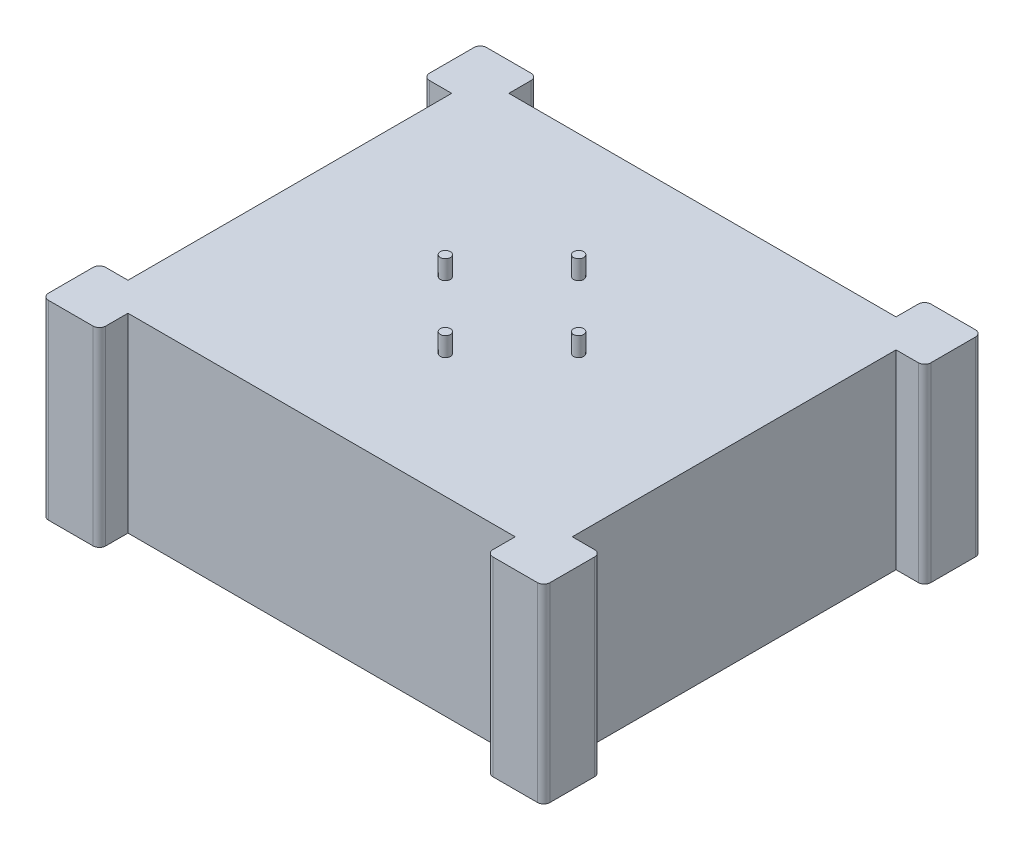
SolidWorks part; units mm, degrees
material "1060 Alloy"
ref_plane "Front Plane" through (0, 0, 0) normal (0, 0, 1) x (1, 0, 0)
ref_plane "Top Plane" through (0, 0, 0) normal (0, 1, 0) x (1, 0, 0)
ref_plane "Right Plane" through (0, 0, 0) normal (1, 0, 0) x (0, 0, -1)
sketch "Sketch1" plane through (0, 0, 0) normal (0, 1, 0) x (1, 0, 0)
  line L0 (-175, 0) -> (175, 0) construction
  line L1 (-175, 150) -> (175, 150)
  line L2 (-175, 150) -> (-175, -150)
  line L3 (-175, -150) -> (175, -150)
  line L4 (175, 150) -> (175, -150)
  line L5 (-175, 172.5) -> (-175, 127.5) construction
  line L6 (-192.5, 172.5) -> (-157.5, 172.5)
  line L7 (-197.5, 167.5) -> (-197.5, 132.5)
  line L8 (-192.5, 127.5) -> (-157.5, 127.5)
  line L9 (-152.5, 167.5) -> (-152.5, 132.5)
  line L10 (157.5, 172.5) -> (192.5, 172.5)
  line L11 (152.5, 167.5) -> (152.5, 132.5)
  line L12 (157.5, 127.5) -> (192.5, 127.5)
  line L13 (197.5, 167.5) -> (197.5, 132.5)
  line L14 (175, 172.5) -> (175, 127.5) construction
  line L15 (157.5, -127.5) -> (192.5, -127.5)
  line L16 (152.5, -132.5) -> (152.5, -167.5)
  line L17 (157.5, -172.5) -> (192.5, -172.5)
  line L18 (197.5, -132.5) -> (197.5, -167.5)
  line L19 (175, -127.5) -> (175, -172.5) construction
  line L20 (-192.5, -127.5) -> (-157.5, -127.5)
  line L21 (-197.5, -132.5) -> (-197.5, -167.5)
  line L22 (-192.5, -172.5) -> (-157.5, -172.5)
  line L23 (-152.5, -132.5) -> (-152.5, -167.5)
  line L24 (-175, -127.5) -> (-175, -172.5) construction
  line L26 (-170, 145) -> (170, 145)
  line L27 (-170, 145) -> (-170, -145)
  line L28 (-170, -145) -> (170, -145)
  line L29 (170, 145) -> (170, -145)
  circle A0 centre (0, 0) radius 52.5 construction
  circle A1 centre (0, 52.5) radius 4
  circle A2 centre (0, -52.5) radius 4
  circle A3 centre (52.5, 0) radius 4
  circle A4 centre (-52.5, 0) radius 4
  arc A5 (-157.5, 172.5) -> (-152.5, 167.5) centre (-157.5, 167.5) cw
  arc A6 (-157.5, 127.5) -> (-152.5, 132.5) centre (-157.5, 132.5) ccw
  arc A7 (-197.5, 132.5) -> (-192.5, 127.5) centre (-192.5, 132.5) ccw
  arc A8 (-192.5, 172.5) -> (-197.5, 167.5) centre (-192.5, 167.5) ccw
  arc A9 (192.5, 172.5) -> (197.5, 167.5) centre (192.5, 167.5) cw
  arc A10 (192.5, 127.5) -> (197.5, 132.5) centre (192.5, 132.5) ccw
  arc A11 (152.5, 132.5) -> (157.5, 127.5) centre (157.5, 132.5) ccw
  arc A12 (157.5, 172.5) -> (152.5, 167.5) centre (157.5, 167.5) ccw
  arc A13 (192.5, -127.5) -> (197.5, -132.5) centre (192.5, -132.5) cw
  arc A14 (192.5, -172.5) -> (197.5, -167.5) centre (192.5, -167.5) ccw
  arc A15 (152.5, -167.5) -> (157.5, -172.5) centre (157.5, -167.5) ccw
  arc A16 (157.5, -127.5) -> (152.5, -132.5) centre (157.5, -132.5) ccw
  arc A17 (-157.5, -127.5) -> (-152.5, -132.5) centre (-157.5, -132.5) cw
  arc A18 (-157.5, -172.5) -> (-152.5, -167.5) centre (-157.5, -167.5) ccw
  arc A19 (-197.5, -167.5) -> (-192.5, -172.5) centre (-192.5, -167.5) ccw
  arc A20 (-192.5, -127.5) -> (-197.5, -132.5) centre (-192.5, -132.5) ccw
  point P31 (-175, 150)
  point P34 (175, -150)
  point P76 (-175, -150)
  dimension "D1" = 105
  dimension "D2" = 8
  dimension "D3" = 8
  dimension "D4" = 8
  dimension "D5" = 8
  dimension "D10" = 5
  dimension "D6" = 350
  dimension "D7" = 300
  dimension "D8" = 45
  dimension "D9" = 45
  dimension "D13" = 5
  dimension "D14" = 5
  dimension "D15" = 5
  dimension "D16" = 5
  dimension "D11" = 2
  dimension "D12" = 2
extrude "Boss-Extrude1" add sketch "Sketch1" against normal blind 3 contours L1 L4 L3 L2
extrude "Boss-Extrude2" add sketch "Sketch1<3>" along normal blind 15 contours A1 | A3 | A2 | A4 region at (0, 0, -52.5) region at (0, 0, 52.5) region at (52.5, 0, 0) region at (-52.5, 0, 0)
sketch "Sketch1<3>" plane through (0, 0, 0) normal (0, 1, 0) x (1, 0, 0) same geometry as "Sketch1"
extrude "Boss-Extrude3" add sketch "Sketch1<4>" against normal blind 150 contours L6 A8 L7 A7 L8 L2 L1 L9 A5 | L12 L29 L15 L4 | L9 L26 L11 L1 | L27 L8 L2 L20 | L20 A20 L21 A19 L22 A18 L23 L3 L2 | L28 L23 L3 L16 | L16 A15 L17 A14 L18 A13 L15 L4 L3 | L13 A10 L12 A11 L11 A12 L10 A9 | L23 A18 L22 A19 L21 A20 L20 A17 | A16 L16 A15 L17 A14 L18 A13 L15 | L8 A6 L9 A5 L6 A8 L7 A7 region at (-178.7138, 0, -153.7138) region at (0, 0, -147.5) region at (-172.5, 0, 0) region at (-178.7138, 0, 153.7138) region at (172.5, 0, 0) region at (0, 0, 147.5) region at (178.7138, 0, 153.7138)
sketch "Sketch1<4>" plane through (0, 0, 0) normal (0, 1, 0) x (1, 0, 0) same geometry as "Sketch1"
sketch "Sketch3" plane through (-175, 0, 0) normal (-1, 0, 0) x (0, 0, 1)
  line L2 (-58.1733, -77.2109) -> (-86.3191, -60.9609) construction
  line L3 (-86.3191, -60.9609) -> (-58.1733, -77.2109) construction
  line L4 (-58.1733, -77.2109) -> (-58.1733, -44.7109) construction
  line L5 (-85.2663, -59.2605) -> (-61.1427, -73.1882)
  line L6 (-60.1723, -44.7725) -> (-60.1723, -72.628)
  line L7 (-31.0803, -59.2605) -> (-55.2038, -73.1882)
  line L8 (-56.1742, -44.7725) -> (-56.1742, -72.628)
  line L9 (-29.0812, -91.6989) -> (-53.2048, -77.7712)
  line L10 (-29.0812, -62.7229) -> (-53.2048, -76.6507)
  line L11 (-56.1742, -109.6494) -> (-56.1742, -81.7939)
  line L12 (-31.0803, -95.1614) -> (-55.2038, -81.2337)
  line L13 (-85.2663, -95.1614) -> (-61.1427, -81.2337)
  line L14 (-60.1723, -109.6494) -> (-60.1723, -81.7939)
  line L15 (-87.2653, -62.7229) -> (-63.1418, -76.6507)
  line L16 (-87.2653, -91.6989) -> (-63.1418, -77.7712)
  circle A0 centre (-58.1733, -77.2109) radius 32.5
  arc A3 (-81.3606, -61.5154) -> (-60.1723, -49.2824) centre (-58.1733, -77.2109) cw
  arc A4 (-78.755, -63.0197) -> (-60.1723, -52.291) centre (-58.1733, -77.2109) cw
  arc A5 (-70.0482, -68.0466) -> (-60.1723, -62.3447) centre (-58.1733, -77.2109) cw
  circle A6 centre (-58.1733, -77.2109) radius 5
  arc A7 (-67.4208, -69.5636) -> (-60.1723, -65.3786) centre (-58.1733, -77.2109) cw
  arc A8 (-56.1742, -49.2824) -> (-34.986, -61.5154) centre (-58.1733, -77.2109) cw
  arc A9 (-56.1742, -52.291) -> (-37.5915, -63.0197) centre (-58.1733, -77.2109) cw
  arc A10 (-56.1742, -62.3447) -> (-46.2983, -68.0466) centre (-58.1733, -77.2109) cw
  arc A11 (-56.1742, -65.3786) -> (-48.9257, -69.5636) centre (-58.1733, -77.2109) cw
  arc A12 (-32.9869, -64.9779) -> (-32.9869, -89.444) centre (-58.1733, -77.2109) cw
  arc A13 (-35.5924, -66.4822) -> (-35.5924, -87.9397) centre (-58.1733, -77.2109) cw
  arc A14 (-44.2992, -71.5091) -> (-44.2992, -82.9128) centre (-58.1733, -77.2109) cw
  arc A15 (-46.9266, -73.026) -> (-46.9266, -81.3959) centre (-58.1733, -77.2109) cw
  arc A16 (-34.986, -92.9064) -> (-56.1742, -105.1395) centre (-58.1733, -77.2109) cw
  arc A17 (-37.5915, -91.4021) -> (-56.1742, -102.1309) centre (-58.1733, -77.2109) cw
  arc A18 (-46.2983, -86.3753) -> (-56.1742, -92.0771) centre (-58.1733, -77.2109) cw
  arc A19 (-48.9257, -84.8583) -> (-56.1742, -89.0433) centre (-58.1733, -77.2109) cw
  arc A20 (-60.1723, -105.1395) -> (-81.3606, -92.9064) centre (-58.1733, -77.2109) cw
  arc A21 (-60.1723, -102.1309) -> (-78.755, -91.4021) centre (-58.1733, -77.2109) cw
  arc A22 (-60.1723, -92.0771) -> (-70.0482, -86.3753) centre (-58.1733, -77.2109) cw
  arc A23 (-60.1723, -89.0433) -> (-67.4208, -84.8583) centre (-58.1733, -77.2109) cw
  arc A24 (-83.3596, -89.444) -> (-83.3596, -64.9779) centre (-58.1733, -77.2109) cw
  arc A25 (-80.7541, -87.9397) -> (-80.7541, -66.4822) centre (-58.1733, -77.2109) cw
  arc A26 (-72.0473, -82.9128) -> (-72.0473, -71.5091) centre (-58.1733, -77.2109) cw
  arc A27 (-69.4199, -81.3959) -> (-69.4199, -73.026) centre (-58.1733, -77.2109) cw
  point P84 (-58.1733, -77.2109)
  dimension "D1" = 65
  dimension "D5" = 10
  dimension "D8" = 10
  dimension "D9" = 20
  dimension "D10" = 28
  dimension "D11" = 12
  dimension "D4" = 60
  dimension "D6" = 2
  dimension "D7" = 2
  dimension "D12" = 6
extrude "Cut-Extrude1" cut sketch "Sketch3" against normal blind 150 contours L16 A24 L15 A0 | L16 A26 L15 A25 | L5 A5 L6 A4 | L5 A3 L6 A0 | L8 A8 L7 A0 | L8 A10 L7 A9 | A11 L8 A6 L7 | A7 L5 A6 L6 | A27 L16 A6 L15 | A23 L14 A6 L13 | A19 L12 A6 L11 | A15 L10 A6 L9 | L10 A14 L9 A13 | L10 A12 L9 A0 | L12 A16 L11 A0 | L12 A18 L11 A17 | L14 A22 L13 A21 | L14 A20 L13 A0 region at (-175, -51.8651, -72.8067) region at (-175, -77.2109, -87.4401) region at (-175, -59.977, -68.1233) region at (-175, -51.8651, -43.5398) region at (-175, -77.2109, -78.0733) region at (-175, -102.5568, -72.8067) region at (-175, -69.2103, -62.7924) region at (-175, -59.977, -48.2233) region at (-175, -77.2109, -28.9064) region at (-175, -77.2109, -67.4116) region at (-175, -94.4449, -68.1233) region at (-175, -102.5568, -43.5398) region at (-175, -69.2103, -53.5541) region at (-175, -77.2109, -38.2732) region at (-175, -85.2116, -62.7924) region at (-175, -94.4449, -48.2233) region at (-175, -77.2109, -48.9349) region at (-175, -85.2116, -53.5541)
